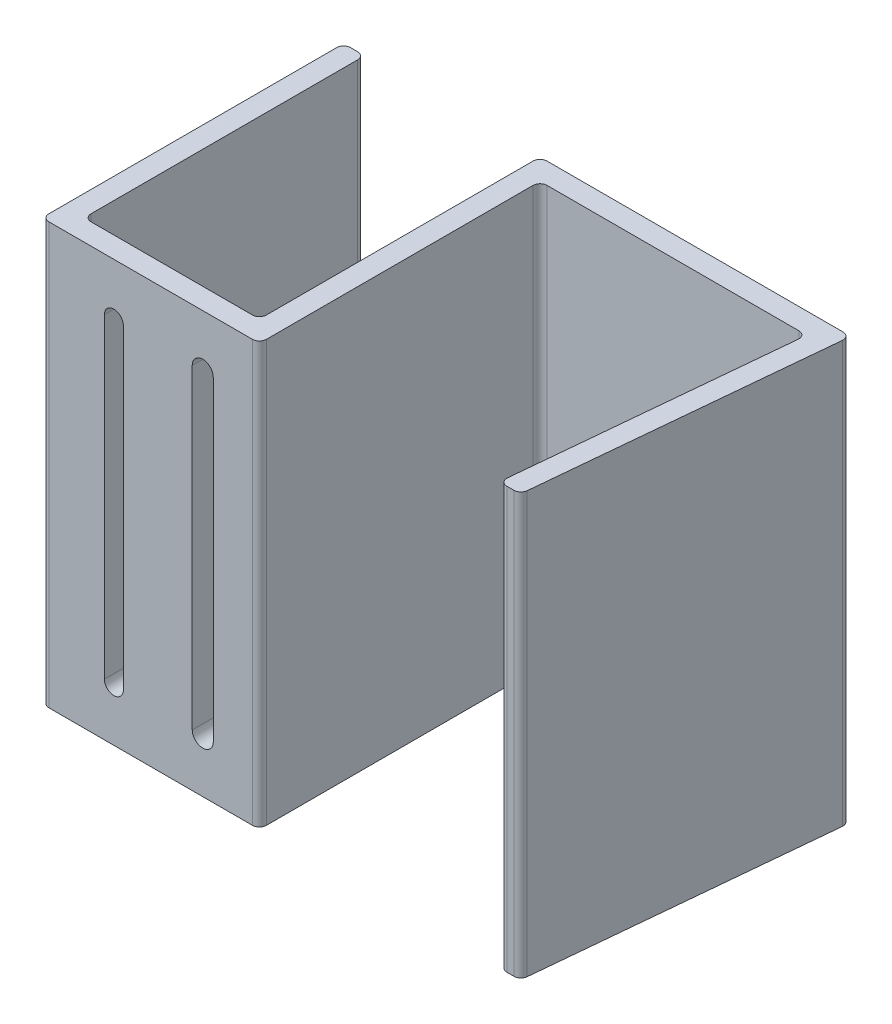
SolidWorks part; units mm, degrees
ref_plane "Plan de face" through (0, 0, 0) normal (0, 0, 1) x (1, 0, 0)
ref_plane "Plan de dessus" through (0, 0, 0) normal (0, 1, 0) x (1, 0, 0)
ref_plane "Plan de droite" through (0, 0, 0) normal (1, 0, 0) x (0, 0, -1)
sketch "Esquisse1" plane through (0, 0, 0) normal (0, 1, 0) x (1, 0, 0)
  line L0 (-21.9608, -19.5168) -> (-21.9608, 20.4832)
  line L1 (16.0392, 20.4832) -> (12.2228, -19.5168)
  line L2 (-21.9608, 20.4832) -> (16.0392, 20.4832)
  line L3 (12.2228, -19.5168) -> (15.2228, -19.5168)
  line L4 (15.2228, -19.5168) -> (19.3254, 23.4832)
  line L5 (19.3254, 23.4832) -> (-24.9608, 23.4832)
  line L6 (-24.9608, 23.4832) -> (-24.9608, -16.5168)
  line L7 (-24.9608, -16.5168) -> (-49.9608, -16.5168)
  line L8 (-49.9608, -16.5168) -> (-49.9608, 23.4832)
  line L9 (-49.9608, 23.4832) -> (-52.9608, 23.4832)
  line L10 (-52.9608, 23.4832) -> (-52.9608, -19.5168)
  line L11 (-52.9608, -19.5168) -> (-21.9608, -19.5168)
  point P2 (-57.6161, -18.5168)
  point P13 (-57.6161, 23.4832)
  point P14 (15.2228, -19.6834)
  point P15 (0, 0)
  dimension "D1" = 40
  dimension "D2" = 38
  dimension "D3" = 3
  dimension "D4" = 3
  dimension "D5" = 3
  dimension "D6" = 3
  dimension "D7" = 25
  dimension "D8" = 3
extrude "Boss.-Extru.1" add sketch "Esquisse1" along normal blind 60
fillet "Congé3" radius 1 12 edges at (16.0392, 30, -20.4832) (-21.9608, 30, -20.4832) (-49.9608, 30, 16.5168) (-24.9608, 30, 16.5168) (-52.9608, 30, 19.5168) (-21.9608, 30, 19.5168) (15.2228, 30, 19.5168) (12.2228, 30, 19.5168) (19.3254, 30, -23.4832) (-24.9608, 30, -23.4832) (-49.9608, 30, -23.4832) (-52.9608, 30, -23.4832)
sketch "Esquisse2" plane through (0, 0, 16.5168) normal (0, 0, -1) x (-1, 0, 0)
  line L0 (25.9608, 60) -> (25.9608, 0) construction
  line L3 (25.9608, 0) -> (48.9608, 0)
  line L4 (25.9608, 0) -> (25.9608, 60)
  line L5 (25.9608, 60) -> (48.9608, 60)
  line L6 (48.9608, 0) -> (48.9608, 60)
  line L7 (25.9608, 0) -> (48.9608, 0) construction
  line L8 (37.4608, 0) -> (37.4608, 60)
  line L9 (30.0387, 7.5) -> (30.0387, 52.5) construction
  line L10 (28.5387, 7.5) -> (28.5387, 52.5)
  line L11 (31.5387, 7.5) -> (31.5387, 52.5)
  line L12 (37.4608, 30) -> (25.9608, 30)
  line L13 (25.9608, 30) -> (48.9608, 30)
  line L14 (42.7114, 7.5) -> (42.7114, 52.5) construction
  line L15 (41.3583, 7.5) -> (41.3583, 52.5)
  line L16 (44.0644, 7.5) -> (44.0644, 52.5)
  arc A2 (28.5387, 7.5) -> (31.5387, 7.5) centre (30.0387, 7.5) ccw
  arc A3 (31.5387, 52.5) -> (28.5387, 52.5) centre (30.0387, 52.5) ccw
  arc A4 (41.3583, 7.5) -> (44.0644, 7.5) centre (42.7114, 7.5) ccw
  arc A5 (44.0644, 52.5) -> (41.3583, 52.5) centre (42.7114, 52.5) ccw
  point P13 (30.0387, 30)
  point P23 (42.7114, 30)
  point P28 (42.7114, 30)
  point P29 (30.0387, 30)
extrude "Enlèv. mat.-Extru.1" cut sketch "Esquisse2" against normal blind 60 contours L15 A5 L16 A4
extrude "Enlèv. mat.-Extru.2" cut sketch "Esquisse2<4>" against normal blind 60 and the other way through all contours L11 A3 L10 A2
sketch "Esquisse2<4>" plane through (0, 0, 16.5168) normal (0, 0, -1) x (-1, 0, 0) same geometry as "Esquisse2"
